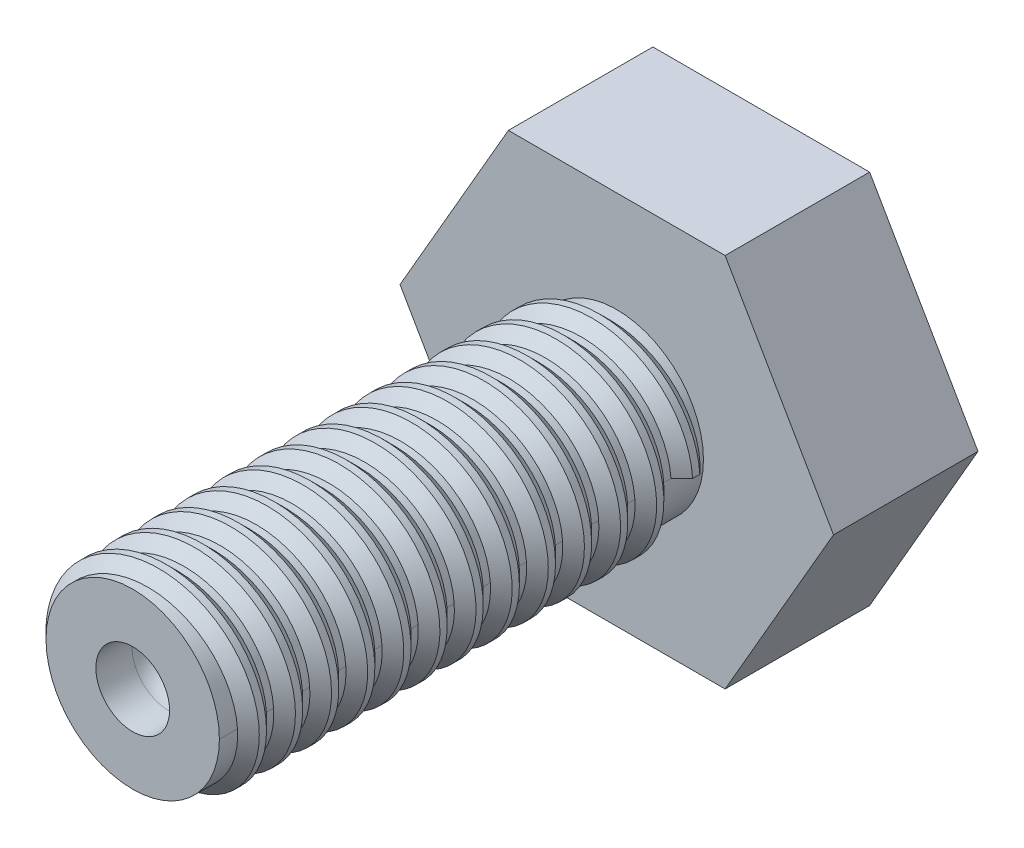
SolidWorks part; units mm, degrees
ref_plane "前视基准面" through (0, 0, 0) normal (0, 0, 1) x (1, 0, 0)
ref_plane "上视基准面" through (0, 0, 0) normal (0, 1, 0) x (1, 0, 0)
ref_plane "右视基准面" through (0, 0, 0) normal (1, 0, 0) x (0, 0, -1)
other "Configuration Table"
sketch "草图1" plane through (0, 0, 0) normal (0, 0, 1) x (1, 0, 0)
  line L13 (15, 0) -> (7.5, 12.9904)
  line L14 (7.5, 12.9904) -> (-7.5, 12.9904)
  line L15 (-7.5, 12.9904) -> (-15, 0)
  line L16 (-15, 0) -> (-7.5, -12.9904)
  line L17 (-7.5, -12.9904) -> (7.5, -12.9904)
  line L18 (7.5, -12.9904) -> (15, 0)
  circle A0 centre (0, 0) radius 15 construction
  dimension "D1" = 30
extrude "凸台-拉伸1" add sketch "草图1" along normal blind 10
sketch "草图2" plane through (0, 0, 10) normal (0, 0, 1) x (1, 0, 0)
  circle A0 centre (0, 0) radius 6
  dimension "D1" = 12
extrude "凸台-拉伸2" add sketch "草图2" along normal blind 33.5
ref_plane "基准面1" through (0, 0, 11.25) normal (0, 0, 1) x (1, 0, 0)
sketch "草图3" plane through (0, 0, 11.25) normal (0, 0, 1) x (1, 0, 0)
  circle A0 centre (0, 0) radius 6 construction
  circle A1 centre (0, 0) radius 6
curve "螺旋线/涡状线1" pitch 2.5 height 31.25 radius 6 centre (0, 0, 11.25) axis (0, 0, 1) start towards (1, 0, 0)
sketch "草图4" plane through (0, 0, 0) normal (0, 1, 0) x (1, 0, 0)
  line L0 (6, -10.25) -> (6, -12.25)
  line L1 (6, -12.25) -> (6.75, -11.5)
  line L2 (6.75, -11.5) -> (6.75, -11)
  line L3 (6.75, -11) -> (6, -10.25)
  point P2 (11.7593, -16.009)
  point P5 (12.3627, -16.3346)
  point P6 (6, -11.25)
  dimension "D1" = 0.75
  dimension "D2" = 2
  dimension "D3" = 45
  dimension "D4" = 45
sweep "扫描1" add profiles "草图4" path "螺旋线/涡状线1"
sketch "草图10" plane through (0, 0, 43.5) normal (0, 0, 1) x (1, 0, 0)
  circle A0 centre (0, 0) radius 2.55
  dimension "D1" = 5.1
extrude "切除-拉伸1" cut sketch "草图10" against normal blind 2.5
sketch "草图11" plane through (0, 0, 41) normal (0, 0, 1) x (1, 0, 0)
  line L0 (0, 2.55) -> (0, -2.55)
  arc A3 (0, -2.55) -> (0, 2.55) centre (0, 0) ccw
  dimension "D1" = 5.1
revolve "切除-旋转1" cut sketch "草图11" angle 360 about L0
